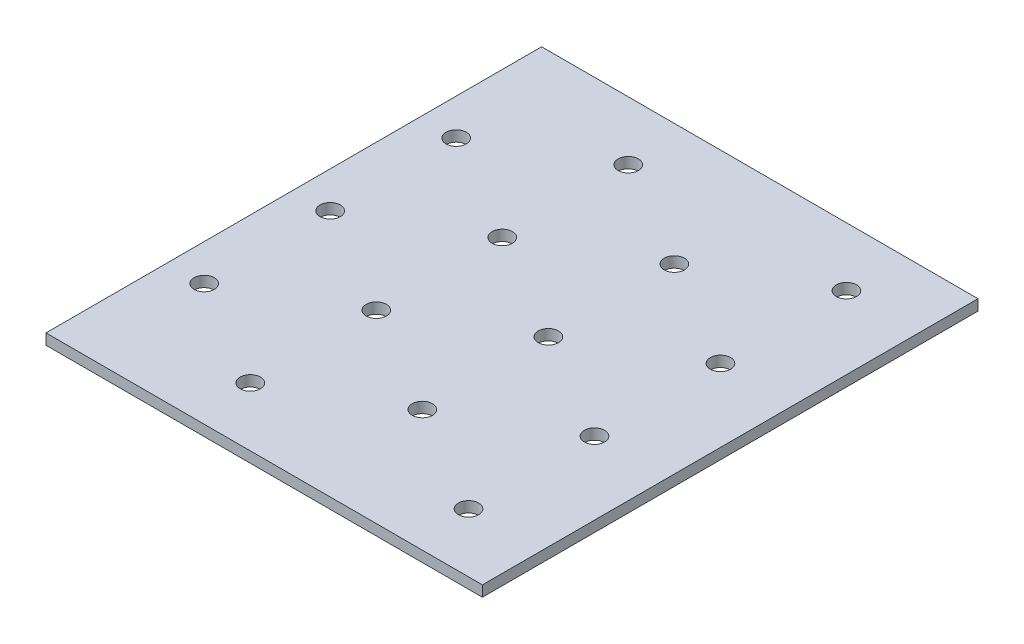
SolidWorks part; units mm, degrees
material "Acrylic (Medium-high impact)"
ref_plane "Front Plane" through (0, 0, 0) normal (0, 0, 1) x (1, 0, 0)
ref_plane "Top Plane" through (0, 0, 0) normal (0, 1, 0) x (1, 0, 0)
ref_plane "Right Plane" through (0, 0, 0) normal (1, 0, 0) x (0, 0, -1)
sketch "Sketch1" plane through (0, 0, 0) normal (0, 1, 0) x (1, 0, 0)
  line L1 (-129, -146.5) -> (129, -146.5)
  line L2 (-129, -146.5) -> (-129, 146.5)
  line L3 (-129, 146.5) -> (129, 146.5)
  line L4 (129, -146.5) -> (129, 146.5)
  line L5 (-129, -146.5) -> (129, 146.5) construction
  line L6 (-129, 146.5) -> (129, -146.5) construction
  point P0 (0, 0)
  dimension "D1" = 293
  dimension "D2" = 258
extrude "Main Base" add sketch "Sketch1" along normal mid plane 6.35
sketch "Base Raft Alignment Sketch" plane through (0, 3.175, 0) normal (0, 1, 0) x (1, 0, 0)
  circle A0 centre (-64.5, 0) radius 49 construction
  circle A1 centre (-107.5, 0) radius 6 construction
  circle A2 centre (-43, 37.2391) radius 6 construction
  circle A3 centre (-43, -37.2391) radius 6 construction
  circle A4 centre (64.5, 0) radius 49 construction
  circle A5 centre (86, 37.2391) radius 6 construction
  circle A6 centre (86, -37.2391) radius 6 construction
  circle A7 centre (21.5, 0) radius 6 construction
  point P7 (-64.5, 0)
  point P13 (-64.5, 0)
  dimension "D1" = 98
  dimension "D3" = 12
  dimension "D2" = 64.5
  dimension "D5" = 2
  dimension "D6" = 64.5
  dimension "D4" = 3
sketch "Raft Alignment Pattern" plane through (0, 3.175, 0) normal (0, 1, 0) x (1, 0, 0)
  line L0 (-107.5, -74.4782) -> (-107.5, 74.4782) construction
  line L1 (-1000, 0) -> (49000, 0) construction
  circle A0 centre (-43, 37.2391) radius 6 construction
  circle A1 centre (-43, 111.7173) radius 6 construction
  circle A2 centre (-107.5, 74.4782) radius 6 construction
  circle A3 centre (-64.5, 74.4782) radius 49 construction
  circle A4 centre (64.5, 74.4782) radius 49 construction
  circle A5 centre (21.5, 74.4782) radius 6 construction
  circle A6 centre (86, 37.2391) radius 6 construction
  circle A7 centre (86, 111.7173) radius 6 construction
  circle A8 centre (86, -111.7173) radius 6 construction
  circle A9 centre (86, -37.2391) radius 6 construction
  circle A10 centre (21.5, -74.4782) radius 6 construction
  circle A11 centre (64.5, -74.4782) radius 49 construction
  circle A12 centre (-64.5, -74.4782) radius 49 construction
  circle A13 centre (-107.5, -74.4782) radius 6 construction
  circle A14 centre (-43, -111.7173) radius 6 construction
  circle A15 centre (-43, -37.2391) radius 6 construction
  point P39 (-107.5, 0)
  dimension "D2" = 98
  dimension "D3" = 12
  dimension "D1" = 64.5
  dimension "D4" = 2
  dimension "D5" = 64.5
sketch "Sketch5" plane through (0, 3.175, 0) normal (0, 1, 0) x (1, 0, 0)
  point P0 (-107.5, 0)
  point P3 (-43, -37.2391)
  point P6 (-43, 37.2391)
  point P10 (86, 37.2391)
  point P13 (21.5, 0)
  point P16 (86, -37.2391)
  point P29 (-107.5, 74.4782)
  point P32 (-43, 111.7173)
  point P35 (21.5, 74.4782)
  point P38 (86, 111.7173)
  point P41 (-107.5, -74.4782)
  point P44 (-43, -111.7173)
  point P47 (21.5, -74.4782)
  point P50 (86, -111.7173)
hole_wizard "Alignment Holes" positions "Sketch5" profile "Sketch6" hole size "Ø12.0" standard "ANSI Metric" end condition through all
sketch "Sketch6" plane through (-107.5, 3.175, 0) normal (1, 0, 0) x (0, 0, 1)
  line L0 (0, 0) -> (0, 6.35)
  line L1 (0, 6.35) -> (6, 6.35)
  line L2 (6, 6.35) -> (6, 0)
  line L5 (6, 0) -> (0, 0)
  line L11 (0, -6.35) -> (0, 107.95) construction
  dimension "Thru Hole Dia." = 12
  dimension "Thru Hole Depth" = 6.35
equation "\"D2@Sketch1\"=64.5*4"
